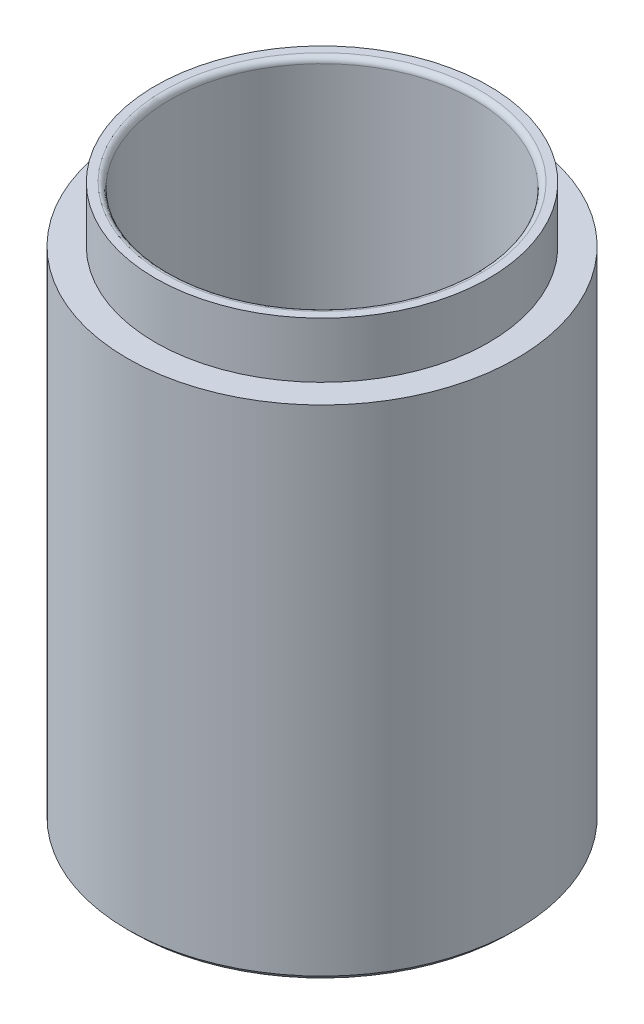
SolidWorks part; units mm, degrees
ref_plane "前视基准面" through (0, 0, 0) normal (0, 0, 1) x (1, 0, 0)
ref_plane "上视基准面" through (0, 0, 0) normal (0, 1, 0) x (1, 0, 0)
ref_plane "右视基准面" through (0, 0, 0) normal (1, 0, 0) x (0, 0, -1)
other "Configuration Table"
sketch "Sketch1" plane through (0, 0, 0) normal (0, 1, 0) x (1, 0, 0)
  circle A0 centre (0, 0) radius 35
  circle A1 centre (0, 0) radius 30
  circle A2 centre (0, 0) radius 27.5
extrude "Boss-Extrude1" add sketch "Sketch1" against normal blind 100 contours A0
extrude "Cut-Extrude1" cut sketch "Sketch1<3>" against normal blind 10 contours A0 A1 region at (-34.0101, 0, 0)
sketch "Sketch1<3>" plane through (0, 0, 0) normal (0, 1, 0) x (1, 0, 0) same geometry as "Sketch1"
extrude "Cut-Extrude2" cut sketch "Sketch1<4>" against normal blind 95 contours A2 region at (0, 0, 0)
sketch "Sketch1<4>" plane through (0, 0, 0) normal (0, 1, 0) x (1, 0, 0) same geometry as "Sketch1"
chamfer "Chamfer1" distance 1 angle 45 1 edges at (0, -100, 35)
fillet "Fillet1" radius 1 1 edges at (0, 0, 27.5)
